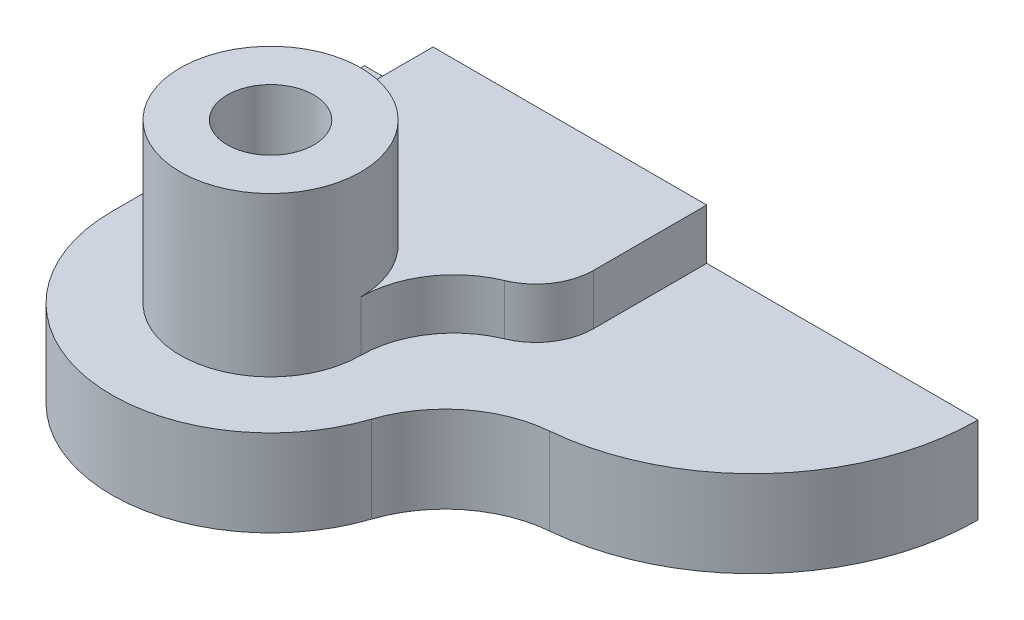
SolidWorks part; units mm, degrees
ref_plane "Front Plane" through (0, 0, 0) normal (0, 0, 1) x (1, 0, 0)
ref_plane "Top Plane" through (0, 0, 0) normal (0, 1, 0) x (1, 0, 0)
ref_plane "Right Plane" through (0, 0, 0) normal (1, 0, 0) x (0, 0, -1)
sketch "Sketch1" plane through (0, 0, 0) normal (0, 1, 0) x (1, 0, 0)
  line L0 (-22, 0) -> (-22, 35)
  line L1 (-22, 35) -> (63, 35)
  line L2 (-12.5, 0) -> (-12.5, 35)
  line L3 (25.4219, 19.3319) -> (25.4219, 35)
  circle A0 centre (0, 0) radius 12.5
  circle A1 centre (0, 0) radius 6
  arc A2 (-22, 0) -> (20.8865, -6.9105) centre (0, 0) ccw
  arc A3 (63, 35) -> (34.6504, 4) centre (31.8761, 35) cw
  arc A4 (34.6504, 4) -> (20.8865, -6.9105) centre (36.0766, -11.9363) ccw
  arc A5 (12.5, 0) -> (20.4809, 11.9399) centre (25.4219, 0) cw
  arc A6 (20.4809, 11.9399) -> (25.4219, 19.3319) centre (17.4219, 19.3319) ccw
  point P19 (24.0864, 0)
  point P21 (0, 0)
  point P22 (25.4219, 0)
  dimension "D1" = 31
  dimension "D4" = 16
  dimension "D5" = 12
  dimension "D6" = 25
  dimension "D7" = 44
  dimension "D8" = 8
  dimension "D2" = 35
  dimension "D3" = 85
extrude "Boss-Extrude1" add sketch "Sketch1" along normal blind 12 contours A6 A5 A0 L2 L1 L0 A2 A4 A3 L3 region at (19.1236, 0, -10.8531)
extrude "Boss-Extrude2" add sketch "Sketch1<3>" along normal blind 19 contours A5 A6 L3 L1 L2 A0 region at (6.1387, 0, -22.3641)
sketch "Sketch1<3>" plane through (0, 0, 0) normal (0, 1, 0) x (1, 0, 0) same geometry as "Sketch1"
extrude "Boss-Extrude3" add sketch "Sketch1<4>" along normal blind 34 contours A0 A1 region at (0, 0, -12.1464)
sketch "Sketch1<4>" plane through (0, 0, 0) normal (0, 1, 0) x (1, 0, 0) same geometry as "Sketch1"
